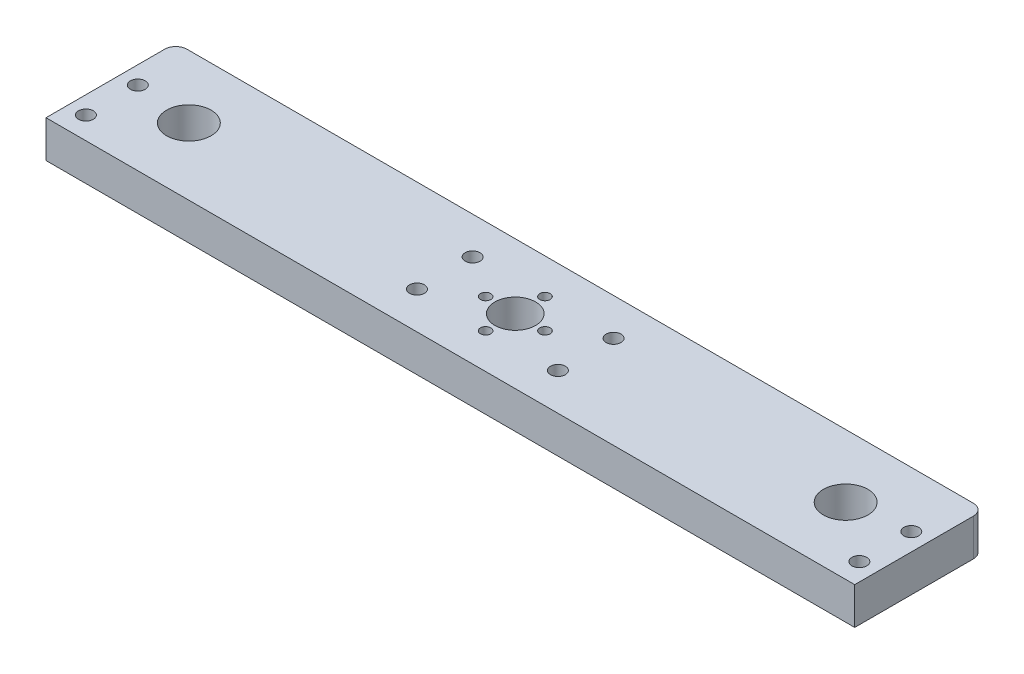
SolidWorks part; units mm, degrees
ref_plane "前视基准面" through (0, 0, 0) normal (0, 0, 1) x (1, 0, 0)
ref_plane "上视基准面" through (0, 0, 0) normal (0, 1, 0) x (1, 0, 0)
ref_plane "右视基准面" through (0, 0, 0) normal (1, 0, 0) x (0, 0, -1)
sketch "草图1" plane through (0, 0, 0) normal (0, 1, 0) x (1, 0, 0)
  line L1 (0, 0) -> (218, 0)
  line L2 (0, 0) -> (0, -35)
  line L3 (0, -35) -> (218, -35)
  line L4 (218, 0) -> (218, -35)
  dimension "D1" = 218
  dimension "D2" = 35
extrude "凸台-拉伸1" add sketch "草图1" along normal blind 10
fillet "圆角1" radius 3 2 edges at (0, 5, 0) (218, 5, 0)
sketch "草图2" plane through (0, 10, 0) normal (0, 1, 0) x (1, 0, 0)
  line L0 (0, -3) -> (0, -35) construction
  line L1 (215, 0) -> (3, 0) construction
  line L2 (0, -35) -> (218, -35) construction
  circle A0 centre (4.75, -15) radius 2
  circle A1 centre (4.75, -29) radius 2
  dimension "D1" = 4
  dimension "D2" = 4.75
  dimension "D3" = 4.75
  dimension "D4" = 15
  dimension "D5" = 6
extrude "切除-拉伸1" cut sketch "草图2" against normal through all
sketch "草图5" plane through (0, 10, 0) normal (0, 1, 0) x (1, 0, 0)
  line L0 (109, 0) -> (109, -35) construction
  line L1 (215, 0) -> (3, 0) construction
  line L2 (0, -35) -> (218, -35) construction
ref_plane "基准面1" through (109, 0, 0) normal (1, 0, 0) x (0, 0, -1)
mirror "镜向5" about plane through (109, 0, 0) normal (1, 0, 0) of "切除-拉伸1"
sketch "草图6" plane through (0, 0, 0) normal (0, -1, 0) x (1, 0, 0)
  line L0 (109, 0) -> (109, 35) construction
  circle A0 centre (109, 17.5) radius 5.5
  dimension "D1" = 11
extrude "切除-拉伸2" cut sketch "草图6" against normal through all
sketch "草图7" plane through (0, 0, 0) normal (0, -1, 0) x (1, 0, 0)
  line L0 (109, 0) -> (109, 35) construction
  circle A0 centre (109, 17.5) radius 5.5
  dimension "D1" = 11
sketch "草图8" plane through (0, 0, 0) normal (0, -1, 0) x (1, 0, 0)
  circle A0 centre (109, 9.5) radius 1.4
  circle A1 centre (117, 17.5) radius 1.4
  circle A2 centre (101, 17.5) radius 1.4
  circle A3 centre (109, 25.5) radius 1.4
  dimension "D1" = 2.8
extrude "切除-拉伸5" cut sketch "草图8" against normal through all
sketch "草图10" plane through (0, 0, 0) normal (0, -1, 0) x (1, 0, 0)
  circle A0 centre (197.5262, 16.97) radius 6
  circle A1 centre (20.4738, 16.97) radius 6
  dimension "D1" = 12
extrude "切除-拉伸6" cut sketch "草图10" against normal through all
sketch "草图11" plane through (0, 0, 0) normal (0, -1, 0) x (1, 0, 0)
  line L0 (0, 35) -> (218, 35) construction
  line L1 (215, 0) -> (3, 0) construction
  line L2 (218, 35) -> (218, 3) construction
  circle A0 centre (128, 10) radius 2
  circle A1 centre (128, 25) radius 2
  dimension "D1" = 4
  dimension "D2" = 10
  dimension "D3" = 10
  dimension "D4" = 90
  dimension "D5" = 90
extrude "切除-拉伸7" cut sketch "草图11" against normal through all
mirror "镜向6" about plane through (109, 0, 0) normal (1, 0, 0) of "切除-拉伸7"
sketch "草图12" plane through (0, 0, 0) normal (0, -1, 0) x (1, 0, 0)
  circle A0 centre (213.25, 15) radius 4
  circle A1 centre (213.25, 29) radius 4
  circle A2 centre (4.75, 15) radius 4
  circle A3 centre (4.75, 29) radius 4
  dimension "D1" = 8
extrude "切除-拉伸8" cut sketch "草图12" against normal blind 5
